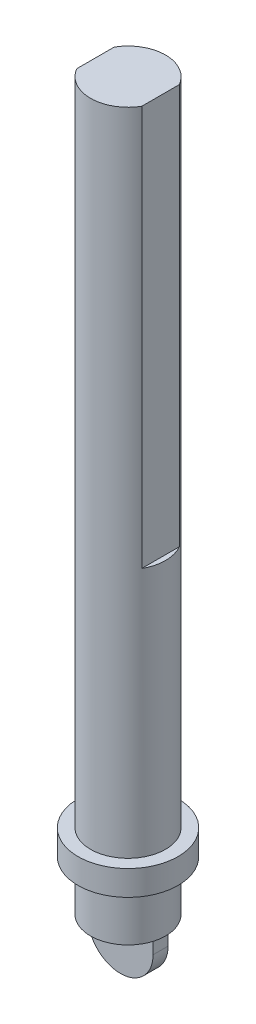
SolidWorks part; units mm, degrees
ref_plane "Front Plane" through (0, 0, 0) normal (0, 0, 1) x (1, 0, 0)
ref_plane "Top Plane" through (0, 0, 0) normal (0, 1, 0) x (1, 0, 0)
ref_plane "Right Plane" through (0, 0, 0) normal (1, 0, 0) x (0, 0, -1)
sketch "Sketch3" plane through (0, 0, 0) normal (0, 1, 0) x (1, 0, 0)
  circle A0 centre (0, 0) radius 7.5
  dimension "D1" = 15
extrude "Boss-Extrude1" add sketch "Sketch3" along normal blind 130
sketch "Sketch4" plane through (0, 0, 0) normal (0, -1, 0) x (1, 0, 0)
  circle A0 centre (0, 0) radius 10
  dimension "D1" = 20
extrude "Boss-Extrude2" add sketch "Sketch4" along normal blind 5
sketch "Sketch5" plane through (0, -5, 0) normal (0, -1, 0) x (1, 0, 0)
  circle A0 centre (0, 0) radius 7.5
  dimension "D1" = 15
extrude "Boss-Extrude3" add sketch "Sketch5" along normal blind 10
sketch "Sketch7" plane through (0, 0, 0) normal (0, 0, 1) x (1, 0, 0)
  line L0 (0, -8.5658) -> (0, -22.8932) construction
  line L1 (-6.5, -15) -> (6.5, -15)
  line L2 (-7.5, -15) -> (7.5, -15) construction
  line L3 (-6.5, -15) -> (-6.5, -18)
  line L4 (6.5, -15) -> (6.5, -18)
  arc A0 (-6.5, -18) -> (6.5, -18) centre (0, -18) ccw
  point P10 (0, -15)
  dimension "D1" = 6.5
  dimension "D2" = 3
extrude "Boss-Extrude4" add sketch "Sketch7" along normal blind 1.5 and the other way blind 1.5
sketch "Sketch8" plane through (0, 130, 0) normal (0, 1, 0) x (1, 0, 0)
  line L0 (6.5, 3.7417) -> (6.5, -3.7417)
  line L1 (0, 10.831) -> (0, -8.5582) construction
  line L2 (-6.5, 3.7417) -> (-6.5, -3.7417)
  circle A0 centre (0, 0) radius 7.5 construction
  circle A1 centre (0, 0) radius 7.5 construction
  arc A2 (6.5, -3.7417) -> (6.5, 3.7417) centre (0, 0) ccw
  arc A3 (-6.5, -3.7417) -> (-6.5, 3.7417) centre (0, 0) cw
  dimension "D1" = 6.5
extrude "Cut-Extrude1" cut sketch "Sketch8" against normal blind 80
